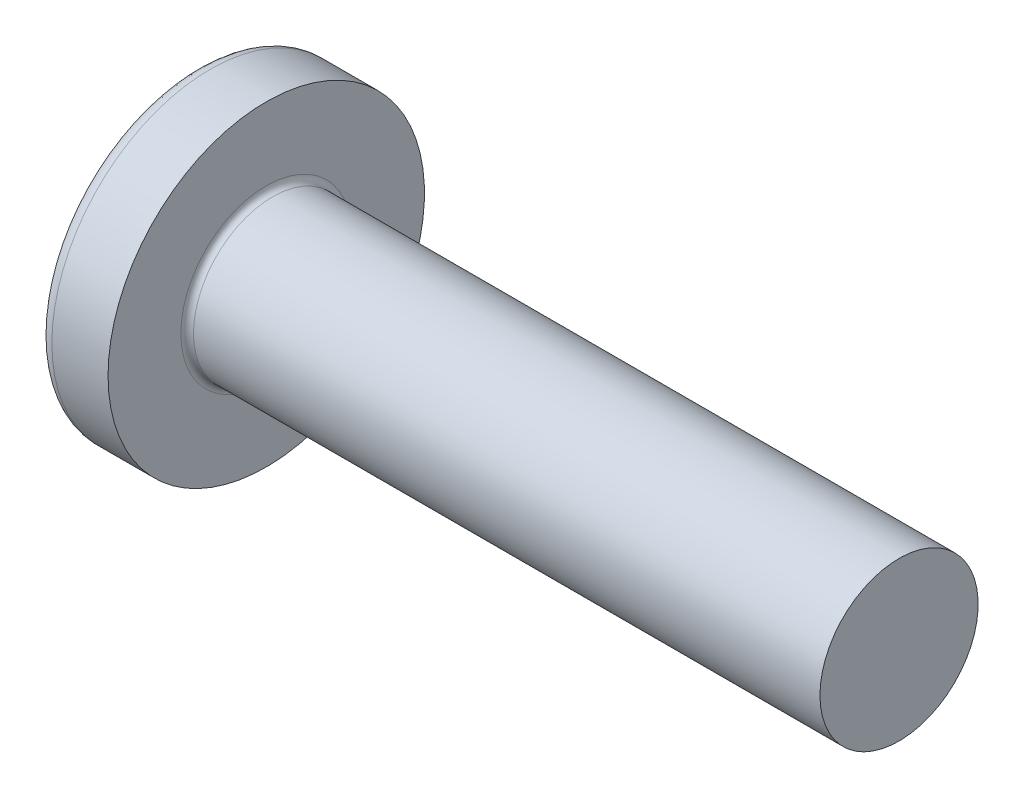
SolidWorks part; units mm, degrees
ref_plane "Front Plane" through (0, 0, 0) normal (0, 0, 1) x (1, 0, 0)
ref_plane "Top Plane" through (0, 0, 0) normal (0, 1, 0) x (1, 0, 0)
ref_plane "Right Plane" through (0, 0, 0) normal (1, 0, 0) x (0, 0, -1)
sketch "BodySke" plane through (0, 0, 0) normal (0, 0, 1) x (1, 0, 0)
  line L0 (0, 0) -> (156.4409, 0) construction
  line L1 (0, 0) -> (0, 48.4317) construction
  line L2 (0, 0) -> (47.5, 0)
  line L3 (47.5, 0) -> (47.5, 5)
  line L4 (47.5, 5) -> (7.5, 5)
  line L5 (7.5, 5) -> (7.5, 10)
  line L6 (7.5, 10) -> (3.9501, 10)
  line L7 (9, 0) -> (9, 8.4138) construction
  line L8 (7.5, 0) -> (7.5, 8.4138) construction
  arc A0 (0, 0) -> (3.2319, 9.6424) centre (16, 0) cw
  arc A1 (3.9501, 10) -> (3.2319, 9.6424) centre (3.9501, 9.1) ccw
  point P14 (47.5, 4.172)
  dimension "Thread_minor" = 8.344
  dimension "Thread_length" = 40
  dimension "Advance" = 1.5
revolve "BaseBody" add sketch "BodySke" angle 360 about L0
cosmetic thread "ThreadCosmetic" [suppressed] parameters "Thread_length"=40, "Thread_minor"=8.344
fillet "Fillet1" radius 0.4 1 edges at (7.5, 0, 5)
ref_plane "Plane1" through (5.69, 0, 0) normal (1, 0, 0) x (0, 0, -1)
sketch "RecessTopSke" plane through (0, 0, 0) normal (1, 0, 0) x (0, 0, -1)
  line L0 (-1.08, 4.95) -> (1.08, -4.95) construction
  line L1 (-1.08, 4.95) -> (1.08, 4.95)
  line L2 (-1.08, 4.95) -> (-1.08, -4.95)
  line L3 (-1.08, -4.95) -> (1.08, -4.95)
  line L4 (1.08, 4.95) -> (1.08, -4.95)
sketch "RecessBottomSke" plane through (5.69, 0, 0) normal (1, 0, 0) x (0, 0, -1)
  line L0 (-1.08, 4.95) -> (-1.08, -4.95) construction
  line L1 (-1.08, -2.1285) -> (1.08, -2.1285)
  line L2 (-1.08, -2.1285) -> (-1.08, 2.1285)
  line L3 (-1.08, 2.1285) -> (1.08, 2.1285)
  line L4 (1.08, -2.1285) -> (1.08, 2.1285)
  line L5 (1.08, 4.95) -> (1.08, -4.95) construction
  line L6 (-1.08, -2.1285) -> (1.08, 2.1285) construction
  dimension "D1" = 4.257
loft "Recess" cut profiles "RecessTopSke", "RecessBottomSke" connector at (0, -4.95, 1.08) connector at (5.69, -2.1285, 1.08)
pattern_circular "RecPat" count 2 over 90 about axis through (0, 0, 0) along (1, 0, 0) of "Recess"
sketch "RecessCoreSke" plane through (0, 0, 0) normal (0, 0, 1) x (1, 0, 0)
  line L0 (0, 0) -> (51.8769, 0) construction
  line L1 (0, 0) -> (6.3173, 0)
  line L2 (6.3173, 0) -> (5.69, 1.9305)
  line L3 (5.69, 1.9305) -> (0, 2.3284)
  line L4 (0, 2.3284) -> (0, 0)
  dimension "D1" = 5.69
  dimension "Diameter" = 3.861
revolve "RecessCore" cut sketch "RecessCoreSke" angle 360 about L0
sketch "ThdSchSke" plane through (0, 0, 0) normal (0, 0, 1) x (1, 0, 0)
  line L0 (0, 0) -> (54.2585, 0) construction
  line L1 (47.022, 5.9561) -> (47.022, 5)
  line L2 (47.022, 5.9561) -> (47.978, 5.9561)
  line L3 (47.978, 5.9561) -> (47.978, 5)
  line L4 (47.978, 5) -> (47.5, 4.172)
  line L5 (47.5, 4.172) -> (47.022, 5)
  line L6 (47.5, 5) -> (7.5, 5) construction
revolve "ThreadSchematic" [suppressed] cut sketch "ThdSchSke" angle 360 about L0
pattern_linear "ThdSchPat" [suppressed] of bodies 117
equation "\"Thread_minor@ThreadCosmetic\" = \"Thread_minor@BodySke\""
equation "\"Thread_length@ThreadCosmetic\" = \"Thread_length@BodySke\""
equation "\"D1@RecessBottomSke\" = \"Cross_diameter@RecessTopSke\"  * 0.43"
equation "\"D1@RecessCoreSke\" = \"Cross_depth@Plane1\""
equation "\"Tooth_Num@ThdSchPat\" =  int( \"Thread_length@BodySke\" / \"Advance@BodySke\" ) "
equation "\"Advance@ThdSchPat\" = \"Advance@BodySke\""
